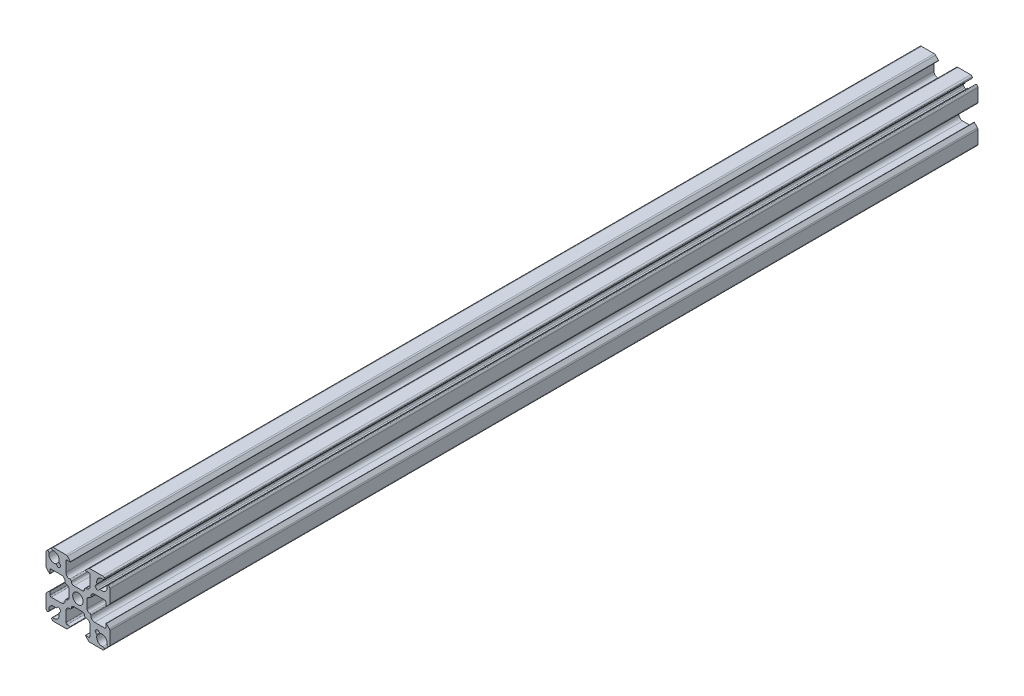
SolidWorks part; units mm, degrees
ref_plane "Front Plane" through (0, 0, 0) normal (0, 0, 1) x (1, 0, 0)
ref_plane "Top Plane" through (0, 0, 0) normal (0, 1, 0) x (1, 0, 0)
ref_plane "Right Plane" through (0, 0, 0) normal (1, 0, 0) x (0, 0, -1)
ref_plane "Plane1" through (0, 0, 0) normal (0, 0, -1) x (-1, 0, 0)
sketch "Sketch1" plane through (0, 0, 0) normal (0, 0, -1) x (-1, 0, 0)
  line L0 (-7.4885, 8.6199) -> (-6.9856, 8.117)
  line L1 (-6.9856, 7.4099) -> (-7.4099, 6.9856)
  line L2 (-8.117, 6.9856) -> (-8.6199, 7.4885)
  line L3 (-12.7, 9.7594) -> (-12.7, 4.7107)
  line L4 (-12.4803, 4.1803) -> (-11.2707, 2.9707)
  line L5 (-11.1, 3.0414) -> (-11.1, 4.325)
  line L6 (-10.6, 4.825) -> (-6.6, 4.825)
  line L7 (-5.1, 3.325) -> (-5.1, 3.15)
  line L8 (-3.6, 1.65) -> (-3.6, -1.65)
  line L9 (-5.1, -3.15) -> (-5.1, -3.325)
  line L10 (-6.6, -4.825) -> (-10.6, -4.825)
  line L11 (-11.1, -4.325) -> (-11.1, -3.0414)
  line L12 (-11.2707, -2.9707) -> (-12.4803, -4.1803)
  line L13 (-12.7, -4.7107) -> (-12.7, -9.7594)
  line L14 (-8.6199, -7.4885) -> (-8.117, -6.9856)
  line L15 (-7.4099, -6.9856) -> (-6.9856, -7.4099)
  line L16 (-6.9856, -8.117) -> (-7.4885, -8.6199)
  line L17 (-9.7594, -12.7) -> (-4.7107, -12.7)
  line L18 (-4.1803, -12.4803) -> (-2.9707, -11.2707)
  line L19 (-3.0414, -11.1) -> (-4.325, -11.1)
  line L20 (-4.825, -10.6) -> (-4.825, -6.6)
  line L21 (-3.325, -5.1) -> (-3.15, -5.1)
  line L22 (-1.65, -3.6) -> (1.65, -3.6)
  line L23 (3.15, -5.1) -> (3.325, -5.1)
  line L24 (4.825, -6.6) -> (4.825, -10.6)
  line L25 (4.325, -11.1) -> (3.0414, -11.1)
  line L26 (2.9707, -11.2707) -> (4.1803, -12.4803)
  line L27 (4.7107, -12.7) -> (9.7594, -12.7)
  line L28 (7.4885, -8.6199) -> (6.9856, -8.117)
  line L29 (6.9856, -7.4099) -> (7.4099, -6.9856)
  line L30 (8.117, -6.9856) -> (8.6199, -7.4885)
  line L31 (12.7, -9.7594) -> (12.7, -4.7107)
  line L32 (12.4803, -4.1803) -> (11.2707, -2.9707)
  line L33 (11.1, -3.0414) -> (11.1, -4.325)
  line L34 (10.6, -4.825) -> (6.6, -4.825)
  line L35 (5.1, -3.325) -> (5.1, -3.15)
  line L36 (3.6, -1.65) -> (3.6, 1.65)
  line L37 (5.1, 3.15) -> (5.1, 3.325)
  line L38 (6.6, 4.825) -> (10.6, 4.825)
  line L39 (11.1, 4.325) -> (11.1, 3.0414)
  line L40 (11.2707, 2.9707) -> (12.4803, 4.1803)
  line L41 (12.7, 4.7107) -> (12.7, 9.7594)
  line L42 (8.6199, 7.4885) -> (8.117, 6.9856)
  line L43 (7.4099, 6.9856) -> (6.9856, 7.4099)
  line L44 (6.9856, 8.117) -> (7.4885, 8.6199)
  line L45 (9.7594, 12.7) -> (4.7107, 12.7)
  line L46 (4.1803, 12.4803) -> (2.9707, 11.2707)
  line L47 (3.0414, 11.1) -> (4.325, 11.1)
  line L48 (4.825, 10.6) -> (4.825, 6.6)
  line L49 (3.325, 5.1) -> (3.15, 5.1)
  line L50 (1.65, 3.6) -> (-1.65, 3.6)
  line L51 (-3.15, 5.1) -> (-3.325, 5.1)
  line L52 (-4.825, 6.6) -> (-4.825, 10.6)
  line L53 (-4.325, 11.1) -> (-3.0414, 11.1)
  line L54 (-2.9707, 11.2707) -> (-4.1803, 12.4803)
  line L55 (-4.7107, 12.7) -> (-9.7594, 12.7)
  circle A0 centre (0, 0) radius 2.08
  arc A1 (-9.7594, 12.7) -> (-10.4266, 12.2927) centre (-9.7594, 11.95) ccw
  arc A2 (-10.4266, 12.2927) -> (-9.8933, 11.5721) centre (-9.9818, 12.0642) ccw
  arc A3 (-9.8933, 11.5721) -> (-7.5492, 8.8748) centre (-9.525, 9.525) cw
  arc A4 (-7.5492, 8.8748) -> (-7.4885, 8.6199) centre (-7.3118, 8.7967) ccw
  arc A5 (-6.9856, 8.117) -> (-6.9856, 7.4099) centre (-7.3392, 7.7635) cw
  arc A6 (-7.4099, 6.9856) -> (-8.117, 6.9856) centre (-7.7635, 7.3392) cw
  arc A7 (-8.6199, 7.4885) -> (-8.8748, 7.5492) centre (-8.7967, 7.3118) ccw
  arc A8 (-8.8748, 7.5492) -> (-11.5721, 9.8933) centre (-9.525, 9.525) cw
  arc A9 (-11.5721, 9.8933) -> (-12.2927, 10.4266) centre (-12.0642, 9.9818) ccw
  arc A10 (-12.2927, 10.4266) -> (-12.7, 9.7594) centre (-11.95, 9.7594) ccw
  arc A11 (-12.7, 4.7107) -> (-12.4803, 4.1803) centre (-11.95, 4.7107) ccw
  arc A12 (-11.2707, 2.9707) -> (-11.1, 3.0414) centre (-11.2, 3.0414) ccw
  arc A13 (-11.1, 4.325) -> (-10.6, 4.825) centre (-10.6, 4.325) cw
  arc A14 (-6.6, 4.825) -> (-5.1, 3.325) centre (-6.6, 3.325) cw
  arc A15 (-5.1, 3.15) -> (-4.6, 2.65) centre (-4.6, 3.15) ccw
  arc A16 (-4.6, 2.65) -> (-3.6, 1.65) centre (-4.6, 1.65) cw
  arc A17 (-3.6, -1.65) -> (-4.6, -2.65) centre (-4.6, -1.65) cw
  arc A18 (-4.6, -2.65) -> (-5.1, -3.15) centre (-4.6, -3.15) ccw
  arc A19 (-5.1, -3.325) -> (-6.6, -4.825) centre (-6.6, -3.325) cw
  arc A20 (-10.6, -4.825) -> (-11.1, -4.325) centre (-10.6, -4.325) cw
  arc A21 (-11.1, -3.0414) -> (-11.2707, -2.9707) centre (-11.2, -3.0414) ccw
  arc A22 (-12.4803, -4.1803) -> (-12.7, -4.7107) centre (-11.95, -4.7107) ccw
  arc A23 (-12.7, -9.7594) -> (-12.2927, -10.4266) centre (-11.95, -9.7594) ccw
  arc A24 (-12.2927, -10.4266) -> (-11.5721, -9.8933) centre (-12.0642, -9.9818) ccw
  arc A25 (-11.5721, -9.8933) -> (-8.8748, -7.5492) centre (-9.525, -9.525) cw
  arc A26 (-8.8748, -7.5492) -> (-8.6199, -7.4885) centre (-8.7967, -7.3118) ccw
  arc A27 (-8.117, -6.9856) -> (-7.4099, -6.9856) centre (-7.7635, -7.3392) cw
  arc A28 (-6.9856, -7.4099) -> (-6.9856, -8.117) centre (-7.3392, -7.7635) cw
  arc A29 (-7.4885, -8.6199) -> (-7.5492, -8.8748) centre (-7.3118, -8.7967) ccw
  arc A30 (-7.5492, -8.8748) -> (-9.8933, -11.5721) centre (-9.525, -9.525) cw
  arc A31 (-9.8933, -11.5721) -> (-10.4266, -12.2927) centre (-9.9818, -12.0642) ccw
  arc A32 (-10.4266, -12.2927) -> (-9.7594, -12.7) centre (-9.7594, -11.95) ccw
  arc A33 (-4.7107, -12.7) -> (-4.1803, -12.4803) centre (-4.7107, -11.95) ccw
  arc A34 (-2.9707, -11.2707) -> (-3.0414, -11.1) centre (-3.0414, -11.2) ccw
  arc A35 (-4.325, -11.1) -> (-4.825, -10.6) centre (-4.325, -10.6) cw
  arc A36 (-4.825, -6.6) -> (-3.325, -5.1) centre (-3.325, -6.6) cw
  arc A37 (-3.15, -5.1) -> (-2.65, -4.6) centre (-3.15, -4.6) ccw
  arc A38 (-2.65, -4.6) -> (-1.65, -3.6) centre (-1.65, -4.6) cw
  arc A39 (1.65, -3.6) -> (2.65, -4.6) centre (1.65, -4.6) cw
  arc A40 (2.65, -4.6) -> (3.15, -5.1) centre (3.15, -4.6) ccw
  arc A41 (3.325, -5.1) -> (4.825, -6.6) centre (3.325, -6.6) cw
  arc A42 (4.825, -10.6) -> (4.325, -11.1) centre (4.325, -10.6) cw
  arc A43 (3.0414, -11.1) -> (2.9707, -11.2707) centre (3.0414, -11.2) ccw
  arc A44 (4.1803, -12.4803) -> (4.7107, -12.7) centre (4.7107, -11.95) ccw
  arc A45 (9.7594, -12.7) -> (10.4266, -12.2927) centre (9.7594, -11.95) ccw
  arc A46 (10.4266, -12.2927) -> (9.8933, -11.5721) centre (9.9818, -12.0642) ccw
  arc A47 (9.8933, -11.5721) -> (7.5492, -8.8748) centre (9.525, -9.525) cw
  arc A48 (7.5492, -8.8748) -> (7.4885, -8.6199) centre (7.3118, -8.7967) ccw
  arc A49 (6.9856, -8.117) -> (6.9856, -7.4099) centre (7.3392, -7.7635) cw
  arc A50 (7.4099, -6.9856) -> (8.117, -6.9856) centre (7.7635, -7.3392) cw
  arc A51 (8.6199, -7.4885) -> (8.8748, -7.5492) centre (8.7967, -7.3118) ccw
  arc A52 (8.8748, -7.5492) -> (11.5721, -9.8933) centre (9.525, -9.525) cw
  arc A53 (11.5721, -9.8933) -> (12.2927, -10.4266) centre (12.0642, -9.9818) ccw
  arc A54 (12.2927, -10.4266) -> (12.7, -9.7594) centre (11.95, -9.7594) ccw
  arc A55 (12.7, -4.7107) -> (12.4803, -4.1803) centre (11.95, -4.7107) ccw
  arc A56 (11.2707, -2.9707) -> (11.1, -3.0414) centre (11.2, -3.0414) ccw
  arc A57 (11.1, -4.325) -> (10.6, -4.825) centre (10.6, -4.325) cw
  arc A58 (6.6, -4.825) -> (5.1, -3.325) centre (6.6, -3.325) cw
  arc A59 (5.1, -3.15) -> (4.6, -2.65) centre (4.6, -3.15) ccw
  arc A60 (4.6, -2.65) -> (3.6, -1.65) centre (4.6, -1.65) cw
  arc A61 (3.6, 1.65) -> (4.6, 2.65) centre (4.6, 1.65) cw
  arc A62 (4.6, 2.65) -> (5.1, 3.15) centre (4.6, 3.15) ccw
  arc A63 (5.1, 3.325) -> (6.6, 4.825) centre (6.6, 3.325) cw
  arc A64 (10.6, 4.825) -> (11.1, 4.325) centre (10.6, 4.325) cw
  arc A65 (11.1, 3.0414) -> (11.2707, 2.9707) centre (11.2, 3.0414) ccw
  arc A66 (12.4803, 4.1803) -> (12.7, 4.7107) centre (11.95, 4.7107) ccw
  arc A67 (12.7, 9.7594) -> (12.2927, 10.4266) centre (11.95, 9.7594) ccw
  arc A68 (12.2927, 10.4266) -> (11.5721, 9.8933) centre (12.0642, 9.9818) ccw
  arc A69 (11.5721, 9.8933) -> (8.8748, 7.5492) centre (9.525, 9.525) cw
  arc A70 (8.8748, 7.5492) -> (8.6199, 7.4885) centre (8.7967, 7.3118) ccw
  arc A71 (8.117, 6.9856) -> (7.4099, 6.9856) centre (7.7635, 7.3392) cw
  arc A72 (6.9856, 7.4099) -> (6.9856, 8.117) centre (7.3392, 7.7635) cw
  arc A73 (7.4885, 8.6199) -> (7.5492, 8.8748) centre (7.3118, 8.7967) ccw
  arc A74 (7.5492, 8.8748) -> (9.8933, 11.5721) centre (9.525, 9.525) cw
  arc A75 (9.8933, 11.5721) -> (10.4266, 12.2927) centre (9.9818, 12.0642) ccw
  arc A76 (10.4266, 12.2927) -> (9.7594, 12.7) centre (9.7594, 11.95) ccw
  arc A77 (4.7107, 12.7) -> (4.1803, 12.4803) centre (4.7107, 11.95) ccw
  arc A78 (2.9707, 11.2707) -> (3.0414, 11.1) centre (3.0414, 11.2) ccw
  arc A79 (4.325, 11.1) -> (4.825, 10.6) centre (4.325, 10.6) cw
  arc A80 (4.825, 6.6) -> (3.325, 5.1) centre (3.325, 6.6) cw
  arc A81 (3.15, 5.1) -> (2.65, 4.6) centre (3.15, 4.6) ccw
  arc A82 (2.65, 4.6) -> (1.65, 3.6) centre (1.65, 4.6) cw
  arc A83 (-1.65, 3.6) -> (-2.65, 4.6) centre (-1.65, 4.6) cw
  arc A84 (-2.65, 4.6) -> (-3.15, 5.1) centre (-3.15, 4.6) ccw
  arc A85 (-3.325, 5.1) -> (-4.825, 6.6) centre (-3.325, 6.6) cw
  arc A86 (-4.825, 10.6) -> (-4.325, 11.1) centre (-4.325, 10.6) cw
  arc A87 (-3.0414, 11.1) -> (-2.9707, 11.2707) centre (-3.0414, 11.2) ccw
  arc A88 (-4.1803, 12.4803) -> (-4.7107, 12.7) centre (-4.7107, 11.95) ccw
extrude "Boss-Extrude1" add sketch "Sketch1" against normal mid plane 345.1098
hole_wizard "Tap Drill for M6x1.0 Tap2" positions "Sketch3" profile "Sketch2" hole size "M6x1.0" standard "ANSI Metric" end condition through all
sketch "Sketch3" plane through (3.6, 0, 0) normal (1, 0, 0) x (0, 0, -1)
  point P0 (-132.5549, -0.0673)
  point P3 (-12.5549, -0.0673)
  point P6 (107.4451, -0.0673)
sketch "Sketch2" plane through (3.6, -0.0673, 132.5549) normal (0, 1, 0) x (0, 0, -1)
  line L0 (0, 0) -> (0, 16.3)
  line L1 (0, 16.3) -> (2.5, 16.3)
  line L2 (2.5, 16.3) -> (2.5, 0)
  line L5 (2.5, 0) -> (0, 0)
  line L11 (0, -6.35) -> (0, 107.95) construction
  dimension "Thru Hole Dia." = 5
  dimension "Thru Hole Depth" = 16.3
hole_wizard "Tap Drill for M6x1.0 Tap1" positions "Sketch5" profile "Sketch4" hole size "M6x1.0" standard "ANSI Metric" end condition through all
sketch "Sketch5" plane through (-3.6, 0, 0) normal (-1, 0, 0) x (0, 0, 1)
  point P0 (151.5376, 0)
  point P3 (31.5376, 0)
  point P6 (-88.4624, 0)
sketch "Sketch4" plane through (-3.6, 0, 151.5376) normal (0, 1, 0) x (0, 0, 1)
  line L0 (0, 0) -> (0, 16.3)
  line L1 (0, 16.3) -> (2.5, 16.3)
  line L2 (2.5, 16.3) -> (2.5, 0)
  line L5 (2.5, 0) -> (0, 0)
  line L11 (0, -6.35) -> (0, 107.95) construction
  dimension "Thru Hole Dia." = 5
  dimension "Thru Hole Depth" = 16.3
